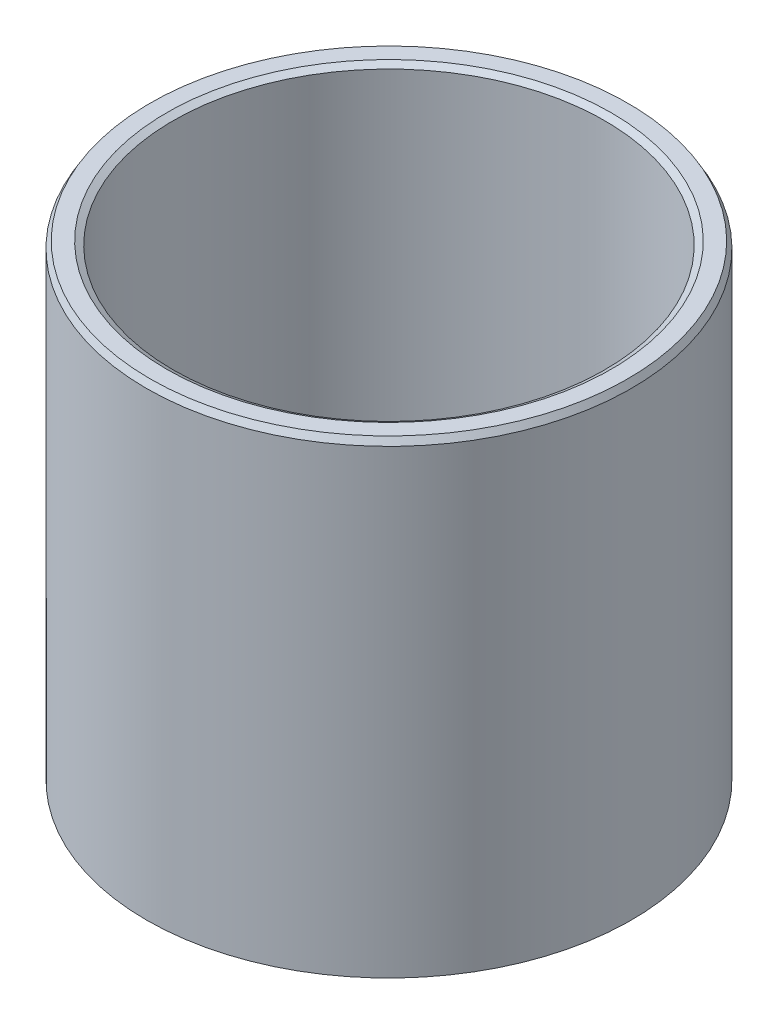
SolidWorks part; units mm, degrees
ref_plane "Front Plane" through (0, 0, 0) normal (0, 0, 1) x (1, 0, 0)
ref_plane "Top Plane" through (0, 0, 0) normal (0, 1, 0) x (1, 0, 0)
ref_plane "Right Plane" through (0, 0, 0) normal (1, 0, 0) x (0, 0, -1)
sketch "Sketch1" plane through (0, 0, 0) normal (0, 1, 0) x (1, 0, 0)
  circle A0 centre (0, 0) radius 55
  dimension "SLEEVE_OD" = 110
extrude "Boss-Extrude1" add sketch "Sketch1" along normal blind 106.7156
sketch "Sketch2" plane through (0, 0, 0) normal (0, 1, 0) x (1, 0, 0)
  circle A0 centre (0, 0) radius 48.9489
  dimension "BORE_D" = 97.8978
extrude "Cut-Extrude1" cut sketch "Sketch2" along normal through all
chamfer "Chamfer1" distance 1.4553 angle 30 4 edges at (0, 106.7156, 48.9489) (0, 0, 48.9489) (0, 0, 55) (0, 106.7156, 55) first distance on face at (0, 106.7156, 48.9489) first distance on face at (0, 0, 48.9489) first distance on face at (0, 106.7156, 55)
